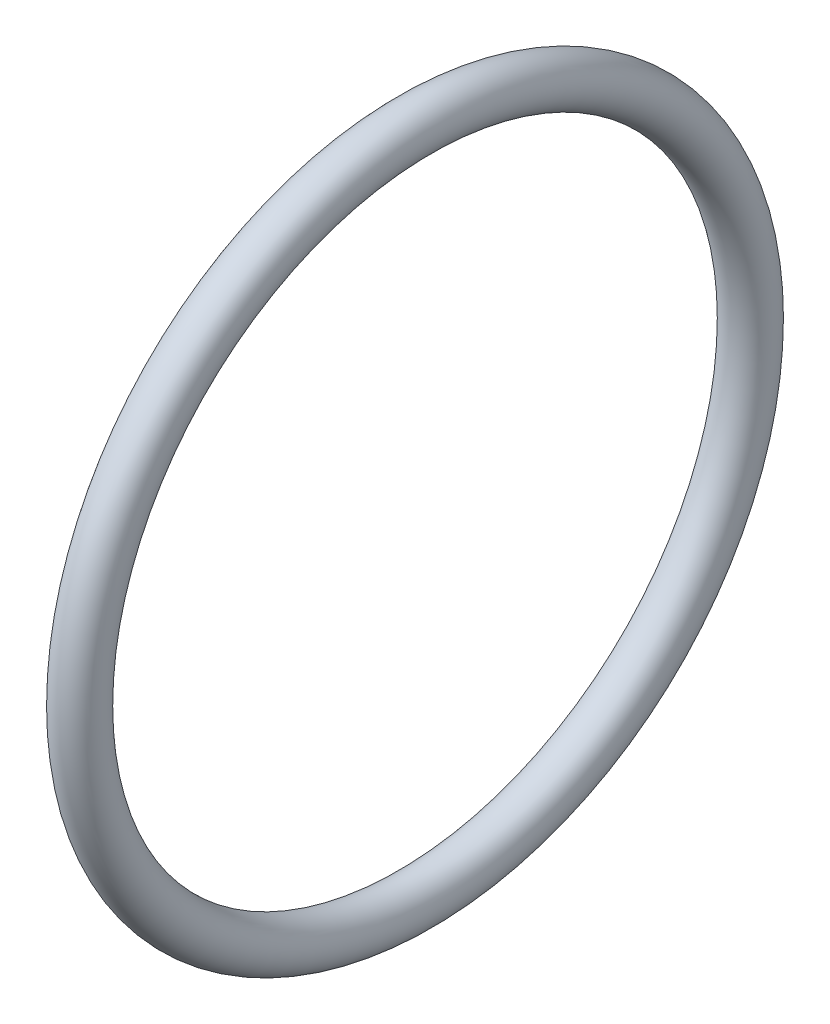
SolidWorks part; units mm, degrees
ref_plane "Front Plane" through (0, 0, 0) normal (0, 0, 1) x (1, 0, 0)
ref_plane "Top Plane" through (0, 0, 0) normal (0, 1, 0) x (1, 0, 0)
ref_plane "Right Plane" through (0, 0, 0) normal (1, 0, 0) x (0, 0, -1)
sketch "Sketch2" plane through (0, 0, 0) normal (0, 0, 1) x (1, 0, 0)
  line L0 (0, 0) -> (58.591, 0) construction
  line L2 (0, 0) -> (18.4, 0)
  line L3 (0, 0) -> (0, 2.5)
  line L4 (0, 2.5) -> (18.4, 2.5)
  line L5 (18.4, 0) -> (18.4, 2.5)
  line L6 (6, 2.5) -> (6, 6)
  line L11 (6, 6) -> (9.97, 6)
  line L16 (12.97, 6) -> (12.97, 3)
  line L17 (12.97, 3) -> (13.6304, 3)
  line L18 (13.6304, 3) -> (13.6304, 2.5)
  line L19 (13.6304, 2.5) -> (6, 2.5)
  line L22 (13.6304, 2.5) -> (16.1104, 2.5)
  line L23 (13.6304, 2.5) -> (13.6304, 4)
  line L24 (13.6304, 4) -> (16.1104, 4)
  line L25 (16.1104, 2.5) -> (16.1104, 4)
  line L27 (6, 6) -> (9.97, 6)
  line L28 (6, 6) -> (6, 9)
  line L29 (6, 9) -> (9.97, 9)
  line L30 (9.97, 6) -> (9.97, 9)
  line L31 (6, 9) -> (6, 8.25)
  line L32 (6, 8.25) -> (5, 8.25)
  line L33 (8.58, 22.001) -> (8.58, 12.476) construction
  line L34 (5, 12.476) -> (12.16, 12.476)
  line L35 (9.97, 9) -> (12.16, 9)
  line L36 (5, 7.5) -> (3, 7.5)
  line L37 (5, 8.25) -> (5, 12.476)
  line L38 (5, 7.5) -> (5, 14)
  line L39 (5, 14) -> (3, 14)
  line L40 (3, 7.5) -> (3, 14)
  line L41 (5, 22.001) -> (12.16, 22.001)
  line L42 (5, 22.001) -> (5, 30.1625)
  line L43 (5, 30.1625) -> (12.16, 30.1625)
  line L44 (12.16, 22.001) -> (12.16, 30.1625)
  line L49 (16.6304, 22.001) -> (16.6304, 7.5)
  line L51 (23.0104, 7.5) -> (23.0104, 6.5)
  line L54 (16.1104, 4) -> (13.6304, 4)
  line L56 (18.0304, 7.5) -> (23.0104, 7.5)
  line L57 (13.16, 22.001) -> (16.6304, 22.001)
  line L58 (16.1104, 3.5) -> (20.0104, 3.5)
  line L59 (29.9004, 14) -> (26.9004, 11)
  line L60 (4, 31.75) -> (18.0304, 31.75)
  line L61 (18.0304, 7.5) -> (23.0104, 7.5)
  line L62 (18.0304, 7.5) -> (18.0304, 12)
  line L63 (18.0304, 12) -> (23.0104, 12)
  line L64 (23.0104, 7.5) -> (23.0104, 12)
  line L65 (18.0304, 31.75) -> (18.0304, 12)
  line L66 (23.0104, 11) -> (26.9004, 11)
  line L67 (34.8004, 23) -> (31.3004, 19.5)
  line L68 (35.8004, 31) -> (38.7904, 33.99)
  line L69 (29.9004, 14) -> (29.9004, 15)
  line L70 (29.9004, 15) -> (22.9304, 15)
  line L71 (22.9304, 15) -> (21.0304, 15)
  line L72 (18.0304, 7.5) -> (16.6304, 7.5)
  line L73 (21.0304, 15) -> (21.0304, 43)
  line L74 (20.0304, 40) -> (10.0704, 40)
  line L75 (10.0704, 40) -> (4, 40)
  line L76 (21.0304, 43) -> (20.0304, 43)
  line L77 (22.9304, 15) -> (29.9004, 15)
  line L78 (22.9304, 15) -> (22.9304, 21)
  line L79 (22.9304, 21) -> (29.9004, 21)
  line L80 (29.9004, 15) -> (29.9004, 21)
  line L81 (10.0704, 40) -> (20.0304, 40)
  line L82 (10.0704, 40) -> (10.0704, 50)
  line L83 (10.0704, 50) -> (20.0304, 50)
  line L84 (20.0304, 40) -> (20.0304, 50)
  line L85 (4, 40) -> (4, 31.75)
  line L86 (12.97, 3) -> (12.97, 2.5)
  line L87 (31.3004, 19.5) -> (29.9004, 19.5)
  line L88 (21.51, 63.5) -> (21.51, 44)
  line L89 (21.51, 63.5) -> (25.9304, 63.5)
  line L90 (25.9304, 63.5) -> (25.9304, 25)
  line L91 (27.8304, 25) -> (25.9304, 25)
  line L92 (10.0704, 48) -> (9, 48)
  line L93 (9, 48) -> (9, 53.476)
  line L94 (9, 53.476) -> (20.0304, 53.476)
  line L95 (20.0304, 53.476) -> (20.0304, 50)
  line L96 (14.5152, 63.001) -> (14.5152, 53.476) construction
  line L97 (9, 63.001) -> (20.0304, 63.001)
  line L98 (9, 63.001) -> (9, 68.2625)
  line L99 (9, 68.2625) -> (20.0304, 68.2625)
  line L100 (20.0304, 63.001) -> (20.0304, 68.2625)
  line L101 (12.97, 6) -> (11.97, 6)
  line L102 (9, 42.5) -> (5, 42.5)
  line L103 (9, 42.5) -> (9, 55)
  line L104 (9, 55) -> (5, 55)
  line L105 (5, 42.5) -> (5, 55)
  line L106 (9.97, 6) -> (10.87, 6)
  line L107 (27.8304, 25) -> (34.8004, 25)
  line L108 (34.8004, 25) -> (34.8004, 23)
  line L109 (0, 0) -> (-2, 0)
  line L110 (0, 0) -> (0, 11)
  line L111 (27.8304, 25) -> (34.8004, 25)
  line L112 (27.8304, 25) -> (27.8304, 32.5)
  line L113 (27.8304, 32.5) -> (34.8004, 32.5)
  line L114 (34.8004, 25) -> (34.8004, 32.5)
  line L115 (35.8004, 31) -> (34.8004, 31)
  line L116 (27.8304, 32.5) -> (27.8304, 64.5)
  line L117 (21.1827, 74.025) -> (6.8477, 74.025)
  line L118 (6.8477, 74.025) -> (6.8477, 76.2)
  line L119 (38.7904, 47.29) -> (30.8304, 55.25)
  line L120 (0, 11) -> (-2, 11)
  line L121 (38.7904, 43.815) -> (30.8529, 43.815)
  line L123 (-4.8, 69.85) -> (1.55, 76.2)
  line L124 (38.7904, 47.29) -> (38.7904, 33.99)
  line L125 (-2, 0) -> (-2, 11)
  line L126 (38.7904, 37.465) -> (30.8529, 37.465)
  line L127 (30.8529, 43.815) -> (30.8529, 37.465)
  line L128 (6, 2.5) -> (6, 0)
  line L129 (0, 63.5) -> (0, 30)
  line L132 (5, 63.5) -> (0, 63.5)
  line L136 (-1.8, 30) -> (-11.76, 30)
  line L138 (-13.76, 25.4) -> (-2, 25.4)
  line L139 (-2, 25.4) -> (-2, 11.5)
  line L140 (27.8304, 64.5) -> (21.1827, 64.5)
  line L141 (-1.8, 30) -> (-11.76, 30)
  line L142 (-1.8, 30) -> (-1.8, 39)
  line L143 (-1.8, 39) -> (-11.76, 39)
  line L144 (-11.76, 30) -> (-11.76, 39)
  line L145 (21.1827, 64.5) -> (21.1827, 74.025)
  line L146 (-12.76, 37) -> (-12.76, 47.29)
  line L147 (-12.76, 37) -> (-11.76, 37)
  line L148 (30.8304, 55.25) -> (30.8304, 76.2)
  line L149 (11.97, 6) -> (11.97, 5.45)
  line L154 (-2, 11.5) -> (1, 11.5)
  line L155 (5, 60.6197) -> (24.05, 60.6197)
  line L160 (5, 60.6197) -> (5, 55.8572)
  line L161 (5, 55.8572) -> (24.05, 55.8572)
  line L166 (24.05, 60.6197) -> (24.05, 55.8572)
  line L167 (5, 60.6197) -> (24.05, 55.8572) construction
  line L172 (5, 55.8572) -> (24.05, 60.6197) construction
  line L173 (24.05, 62.2072) -> (25.9304, 62.2072)
  line L174 (11.97, 5.45) -> (10.87, 5.45)
  line L175 (10.87, 6) -> (10.87, 5.45)
  line L176 (24.05, 62.2072) -> (24.05, 54.2697)
  line L177 (24.05, 54.2697) -> (25.9304, 54.2697)
  line L178 (25.9304, 62.2072) -> (25.9304, 54.2697)
  line L179 (24.05, 62.2072) -> (25.9304, 54.2697) construction
  line L180 (24.05, 54.2697) -> (25.9304, 62.2072) construction
  line L181 (3, 19.6197) -> (15.7, 19.6197)
  line L182 (3, 19.6197) -> (3, 14.8572)
  line L183 (3, 14.8572) -> (15.7, 14.8572)
  line L184 (15.7, 19.6197) -> (15.7, 14.8572)
  line L185 (3, 19.6197) -> (15.7, 14.8572) construction
  line L186 (3, 14.8572) -> (15.7, 19.6197) construction
  line L187 (15.7, 21.2072) -> (16.6304, 21.2072)
  line L188 (15.7, 21.2072) -> (15.7, 13.2697)
  line L189 (15.7, 13.2697) -> (16.6304, 13.2697)
  line L190 (16.6304, 21.2072) -> (16.6304, 13.2697)
  line L191 (15.7, 21.2072) -> (16.6304, 13.2697) construction
  line L192 (15.7, 13.2697) -> (16.6304, 21.2072) construction
  line L193 (1, 11.5) -> (1, 6.5)
  line L194 (1, 6.5) -> (3, 6.5)
  line L195 (23.0104, 6.5) -> (20.0104, 3.5)
  line L196 (5, 63.5) -> (5, 42.5)
  line L197 (5, 42.5) -> (3, 42.5)
  line L198 (3, 42.5) -> (3, 6.5)
  line L199 (6, 0) -> (12.97, 0)
  line L200 (12.97, 0) -> (12.97, 2.5)
  line L201 (18.0304, 31.75) -> (18.0304, 35.875)
  line L202 (18.0304, 35.875) -> (21.0304, 35.875)
  line L203 (30.8304, 76.2) -> (6.8477, 76.2)
  line L204 (3.4027, 69.85) -> (7.8477, 69.85) construction
  line L205 (7.8477, 67.4687) -> (26.8977, 67.4688)
  line L206 (7.8477, 74.025) -> (7.8477, 64.5)
  line L207 (7.8477, 64.5) -> (-1.8, 64.5)
  line L208 (-1.8, 64.5) -> (-1.8, 39)
  line L209 (-12.76, 47.29) -> (-4.8, 55.25)
  line L210 (-4.8, 55.25) -> (-4.8, 69.85)
  line L211 (7.8477, 67.4687) -> (7.8477, 72.2313)
  line L212 (7.8477, 72.2313) -> (26.8977, 72.2313)
  line L213 (26.8977, 67.4688) -> (26.8977, 72.2313)
  line L214 (26.8977, 73.8187) -> (30.8304, 73.8187)
  line L215 (26.8977, 73.8187) -> (26.8977, 65.8813)
  line L216 (26.8977, 65.8813) -> (30.8304, 65.8813)
  line L217 (30.8304, 73.8187) -> (30.8304, 65.8813)
  line L218 (3.4027, 72.2313) -> (25.6277, 72.2313)
  line L219 (3.4027, 72.2313) -> (3.4027, 67.4687)
  line L220 (3.4027, 67.4687) -> (25.6277, 67.4687)
  line L221 (25.6277, 72.2313) -> (25.6277, 67.4687)
  line L222 (25.6277, 69.85) -> (21.1827, 69.85) construction
  line L223 (21.51, 44) -> (22.9304, 44)
  line L224 (22.9304, 44) -> (22.9304, 21)
  line L225 (13.6304, 4) -> (13.6304, 12.2697)
  line L226 (13.6304, 12.2697) -> (13.16, 12.2697)
  line L227 (13.16, 12.2697) -> (13.16, 22.001)
  line L228 (12.16, 9) -> (12.16, 12.476)
  line L229 (-1.8, 30) -> (0, 30)
  line L230 (9, 65.6317) -> (3.4027, 65.6317) construction
  line L231 (20.0304, 65.6317) -> (25.6277, 65.6317) construction
  line L232 (1.55, 76.2) -> (6.8477, 76.2)
  line L233 (-11.76, 30) -> (-13.76, 30)
  line L234 (-13.76, 30) -> (-13.76, 25.4)
  circle A0 centre (26.8804, 25.95) radius 0.95
  circle A1 centre (21.9804, 15.95) radius 0.95
  circle A2 centre (17.3304, 8.2) radius 0.7
  circle A3 centre (10.42, 6.45) radius 0.45
  circle A4 centre (-0.9, 30.9) radius 0.9
  point P7 (24.9902, 58.2385)
  point P131 (16.1652, 17.2385)
  point P135 (14.525, 58.2385)
  point P146 (9.35, 17.2385)
sketch "Sketch3" plane through (0, 0, 0) normal (0, 0, 1) x (1, 0, 0)
  circle A0 centre (10.42, 6.45) radius 0.45 construction
  circle A1 centre (10.42, 6.45) radius 0.45
revolve "Revolve1" add sketch "Sketch3" angle 360 about L0
